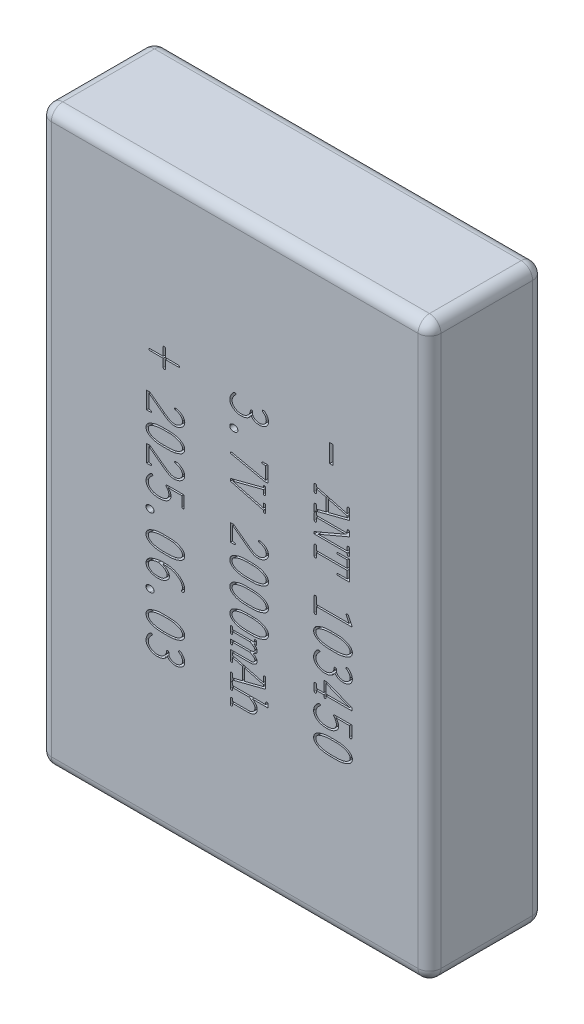
SolidWorks part; units mm, degrees
ref_plane "Front Plane" through (0, 0, 0) normal (1, 0, 0) x (0, 1, 0)
ref_plane "Top Plane" through (0, 0, 0) normal (0, 0, 1) x (0, 1, 0)
ref_plane "Right Plane" through (0, 0, 0) normal (0, 1, 0) x (-1, 0, 0)
sketch "Sketch3" plane through (0, 0, 0) normal (0, 0, 1) x (0, 1, 0)
  line L1 (0, 0) -> (50, 0)
  line L2 (0, 0) -> (0, 34)
  line L3 (0, 34) -> (50, 34)
  line L4 (50, 0) -> (50, 34)
extrude "Boss-Extrude3" add sketch "Sketch3" along normal blind 10 contours L2 L1 L4 L3
fillet "Fillet1" radius 1 4 edges at (0, 0, 5) (0, 25, 0) (0, 50, 5) (0, 25, 10) type face fillet first side face at (0, 25, 5) second side face at (-17, 25, 0) second side face at (-17, 50, 5) second side face at (-34, 25, 5) second side face at (-17, 0, 5) second side face at (-17, 25, 10)
fillet "Fillet2" radius 1 4 edges at (-34, 0, 5) (-34, 25, 10) (-17.5, 0, 0) (-17.5, 50, 10) type face fillet first side face at (-17.5, 25, 10) first side face at (-17.5, 0, 5) second side face at (-17.5, 50, 5) second side face at (-34, 25, 5) second side face at (-17.5, 25, 0)
fillet "Fillet3" radius 1 1 edges at (-17, 0, 10) type face fillet first side face at (-17, 24.5, 10) second side face at (-17, 0, 5.5)
fillet "Fillet4" radius 1 1 edges at (-34, 25.5, 0) type face fillet first side face at (-34, 25.5, 4.5) second side face at (-17.5, 25.5, 0)
fillet "Fillet5" radius 1 1 edges at (-34, 50, 5) type face fillet first side face at (-34, 25.5, 5) second side face at (-20.6414, 50, 3.7586)
sketch "Sketch4" plane through (0, 0, 10) normal (0, 0, 1) x (1, 0, 0)
  text T0 "- ANT 103450\r\n   3.7V 2000mAh\r\n+ 2025.06.03" font "Courier New" height in points 12
extrude "Cut-Extrude2" cut sketch "Sketch4" against normal blind 1
